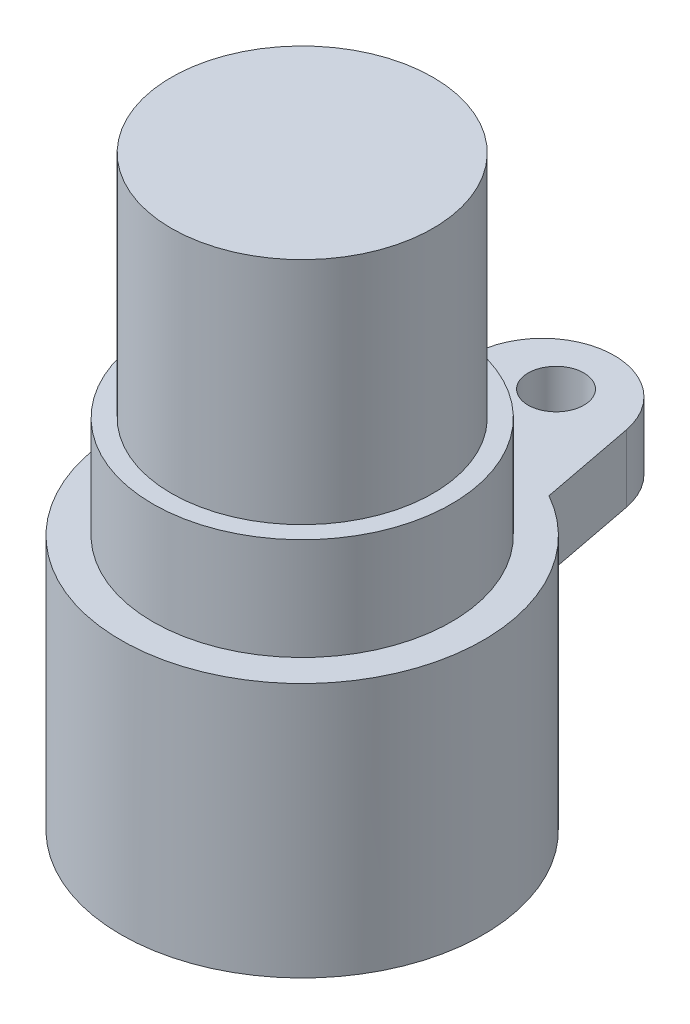
SolidWorks part; units mm, degrees
ref_plane "Front Plane" through (0, 0, 0) normal (0, 0, 1) x (1, 0, 0)
ref_plane "Top Plane" through (0, 0, 0) normal (0, 1, 0) x (1, 0, 0)
ref_plane "Right Plane" through (0, 0, 0) normal (1, 0, 0) x (0, 0, -1)
sketch "Sketch1" plane through (0, 0, 0) normal (0, 1, 0) x (1, 0, 0)
  line L0 (0, 0) -> (0, 18.9122) construction
  line L1 (-5.25, 18.9122) -> (5.25, 18.9122) construction
  line L2 (-5.25, 18.9122) -> (-6.6205, 11.7651)
  line L3 (5.25, 18.9122) -> (6.6205, 11.7651)
  circle A0 centre (0, 0) radius 13.5
  circle A1 centre (0, 0) radius 11.125
  circle A2 centre (0, 0) radius 9.75
  circle A3 centre (0, 18.9122) radius 2.08
  arc A4 (-5.25, 18.9122) -> (5.25, 18.9122) centre (0, 17.9054) cw
  point P12 (4.7469, 12.5423)
  point P13 (0, 18.9122)
  point P14 (-6.6205, 11.7651)
  dimension "D1" = 27
  dimension "D2" = 22.25
  dimension "D3" = 19.5
  dimension "D4" = 4.16
  dimension "D5" = 10.5
extrude "Boss-Extrude1" add sketch "Sketch1" along normal blind 19 contours A0
extrude "Boss-Extrude2" add sketch "Sketch1<3>" along normal blind 7.6 from surface contours A1 starting at face at (0, 19, 13.5)
sketch "Sketch1<3>" plane through (0, 0, 0) normal (0, 1, 0) x (1, 0, 0) same geometry as "Sketch1"
extrude "Boss-Extrude3" add sketch "Sketch1<4>" along normal blind 17.1 from surface contours A2 region at (0, 0, 0) starting at face at (0, 26.6, 11.125)
sketch "Sketch1<4>" plane through (0, 0, 0) normal (0, 1, 0) x (1, 0, 0) same geometry as "Sketch1"
extrude "Boss-Extrude4" add sketch "Sketch1<5>" against normal blind 6 from surface contours A4 L2 A0 L3 A3 region at (0, 0, -23.0758) starting at face at (0, 19, 11.125)
sketch "Sketch1<5>" plane through (0, 0, 0) normal (0, 1, 0) x (1, 0, 0) same geometry as "Sketch1"
chamfer "Chamfer1" distance 1 angle 45 3 edges at (5.9353, 13, -15.3387) (-5.9353, 13, -15.3387) (0, 13, -23.2511)
